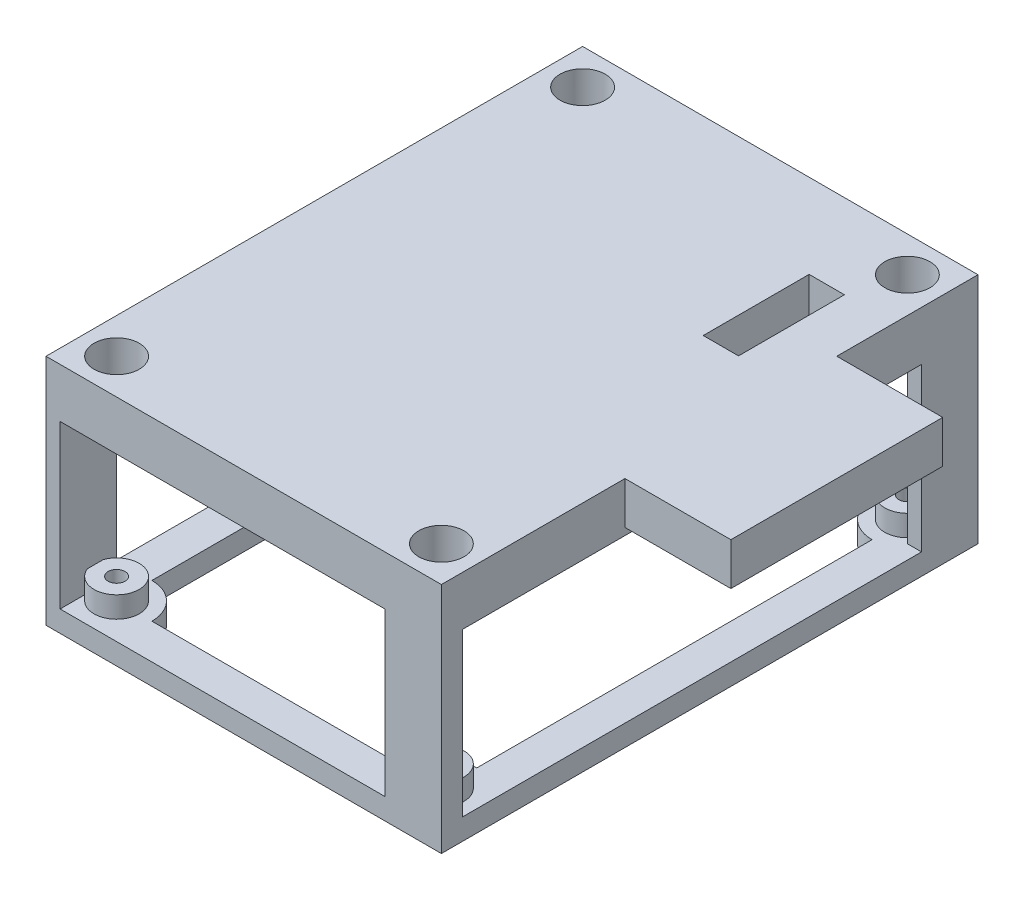
SolidWorks part; units mm, degrees
ref_plane "Front Plane" through (0, 0, 0) normal (0, 0, 1) x (1, 0, 0)
ref_plane "Top Plane" through (0, 0, 0) normal (0, 1, 0) x (1, 0, 0)
ref_plane "Right Plane" through (0, 0, 0) normal (1, 0, 0) x (0, 0, -1)
sketch "Sketch1" plane through (0, 0, 0) normal (0, 1, 0) x (1, 0, 0)
  line L0 (51, 71) -> (51, 5) construction
  line L1 (0, 0) -> (56, 0)
  line L2 (0, 0) -> (0, 76)
  line L3 (0, 76) -> (56, 76)
  line L4 (56, 0) -> (56, 76)
  line L5 (5, 5) -> (51, 5) construction
  line L6 (10, 71) -> (46, 71)
  line L11 (5, 66) -> (5, 10)
  line L12 (10, 5) -> (46, 5)
  line L13 (51, 66) -> (51, 10)
  line L19 (56, 56) -> (71, 56)
  line L20 (56, 56) -> (56, 26)
  line L21 (56, 26) -> (71, 26)
  line L22 (71, 56) -> (71, 26)
  line L23 (44, 64.0837) -> (49, 64.0837)
  line L24 (44, 64.0837) -> (44, 49.0837)
  line L25 (44, 49.0837) -> (49, 49.0837)
  line L26 (49, 64.0837) -> (49, 49.0837)
  circle A0 centre (5, 71) radius 1.2
  circle A1 centre (51, 71) radius 1.2
  circle A2 centre (5, 5) radius 1.2
  circle A3 centre (51, 5) radius 1.2
  circle A4 centre (5, 71) radius 3.2
  circle A5 centre (51, 71) radius 3.2
  circle A6 centre (5, 5) radius 3.2
  circle A7 centre (51, 5) radius 3.2
  arc A8 (5, 66) -> (10, 71) centre (5, 71) ccw
  arc A9 (46, 71) -> (51, 66) centre (51, 71) ccw
  arc A10 (51, 10) -> (46, 5) centre (51, 5) ccw
  arc A11 (10, 5) -> (5, 10) centre (5, 5) ccw
  point P13 (51, 38)
  point P14 (56, 38)
  point P15 (28, 5)
  point P16 (28, 0)
  dimension "D3" = 2.4
  dimension "D4" = 46
  dimension "D5" = 66
  dimension "D6" = 6.4
  dimension "D7" = 20
  dimension "D8" = 30
  dimension "D9" = 2
  dimension "D12" = 5
  dimension "D1" = 56
  dimension "D2" = 76
  dimension "D10" = 46
  dimension "D11" = 66
  dimension "D13" = 5
  dimension "D14" = 7
  dimension "D15" = 15
  dimension "D16" = 15
extrude "Main Outer Connection" add sketch "Sketch1" along normal blind 33 contours L1 L4 L3 L2 A3 A2 A1 A0 L12 A11 L11 A8 L6 A9 L13 A10 | A6 A2 | A7 A3 | A4 A0 | A5 A1 | L6 A9 L13 A10 L12 A11 L11 A8 region at (0.944, 0, -38) region at (1.8905, 0, -71) region at (47.8905, 0, -71) region at (1.8905, 0, -5) region at (47.8905, 0, -5)
sketch "Sketch2" plane through (0, 0, -76) normal (0, 0, -1) x (-1, 0, 0)
  line L1 (-54, 26) -> (-2, 26)
  line L2 (-54, 26) -> (-54, 3)
  line L3 (-54, 3) -> (-2, 3)
  line L4 (-2, 26) -> (-2, 3)
  line L5 (0, 33) -> (-56, 33) construction
  line L7 (-56, 33) -> (-56, 0) construction
  line L8 (0, 33) -> (0, 0) construction
  line L9 (0, 0) -> (-56, 0) construction
  dimension "D1" = 7
  dimension "D2" = 3
  dimension "D3" = 2
  dimension "D4" = 2
extrude "Hole for Protoboard Access" cut sketch "Sketch2" against normal through all
sketch "Sketch16" plane through (0, 0, 0) normal (0, 0, 1) x (1, 0, 0)
  line L0 (54, 3) -> (2, 3) construction
  line L1 (54, 26) -> (48, 26)
  line L2 (54, 26) -> (54, 3)
  line L3 (54, 3) -> (48, 3)
  line L4 (48, 26) -> (48, 3)
  dimension "D1" = 6
extrude "Wall for Screw Terminal Replace" add sketch "Sketch16" against normal blind 2 contours L4 L3 L2 L1
sketch "Sketch18" plane through (56, 0, 0) normal (1, 0, 0) x (0, 0, -1)
  line L0 (0, 33) -> (0, 0) construction
  line L1 (3, 26) -> (68, 26)
  line L2 (3, 26) -> (3, 3)
  line L3 (3, 3) -> (68, 3)
  line L4 (68, 26) -> (68, 3)
  line L5 (76, 33) -> (76, 0) construction
  line L8 (0, 33) -> (76, 33) construction
  line L9 (3, 26) -> (8, 26)
  line L10 (3, 26) -> (3, 3)
  line L11 (3, 3) -> (8, 3)
  line L12 (8, 26) -> (8, 3)
  point P16 (81.6398, 29.1263)
  dimension "D1" = 3
  dimension "D2" = 8
  dimension "D4" = 7
  dimension "D5" = 8
extrude "Hole for Wire Connections" cut sketch "Sketch18" against normal through all contours L1 L12 L3 L4 region at (56, 14.5, -38)
extrude "Hole for Screw Terminal Replace" cut sketch "Sketch18<3>" against normal up to next contours L12 L1 L2 L3 region at (56, 14.5, -5.5)
sketch "Sketch18<3>" plane through (56, 0, 0) normal (1, 0, 0) x (0, 0, -1) same geometry as "Sketch18"
extrude "Hole for Wire in Bottom" cut sketch "Sketch1<3>" along normal up to next contours A11 L12 A10 L13 A9 L6 A8 L11 | L24 L25 L13 L23 region at (27.5186, 0, -37.5165) region at (46.5, 0, -56.5837)
sketch "Sketch1<3>" plane through (0, 0, 0) normal (0, 1, 0) x (1, 0, 0) same geometry as "Sketch1"
extrude "Bolt Head Clearance" cut sketch "Sketch1<5>" against normal up to surface (-26 mm away) from surface contours A7 A3 | A6 A2 | A4 A0 | A5 A1 region at (1.8905, 0, -71) region at (47.8905, 0, -71) region at (1.8905, 0, -5) region at (47.8905, 0, -5) up to face at (5, 26, -3.8) starting at face at (28, 33, -38)
sketch "Sketch1<5>" plane through (0, 0, 0) normal (0, 1, 0) x (1, 0, 0) same geometry as "Sketch1"
extrude "Boss-Extrude6" add sketch "Sketch1<6>" along normal blind 3 from surface contours A6 A2 | A7 A3 | A5 A1 | A4 A0 region at (1.8905, 0, -71) region at (47.8905, 0, -71) region at (1.8905, 0, -5) region at (47.8905, 0, -5) starting at face at (28, 3, -38)
sketch "Sketch1<6>" plane through (0, 0, 0) normal (0, 1, 0) x (1, 0, 0) same geometry as "Sketch1"
extrude "Boss-Extrude7" add sketch "Sketch1<8>" against normal blind 6 from surface contours L22 L19 L4 L21 region at (63.5, 0, -41) starting at face at (51, 33, -67.8)
sketch "Sketch1<8>" plane through (0, 0, 0) normal (0, 1, 0) x (1, 0, 0) same geometry as "Sketch1"
extrude "Cut-Extrude14" cut sketch "Sketch1<9>" against normal up to surface (-26 mm away) from surface contours L26 L25 L24 L23 up to face at (29.8273, 26, -34.2818) starting at face at (51, 33, -67.8)
sketch "Sketch1<9>" plane through (0, 0, 0) normal (0, 1, 0) x (1, 0, 0) same geometry as "Sketch1"
